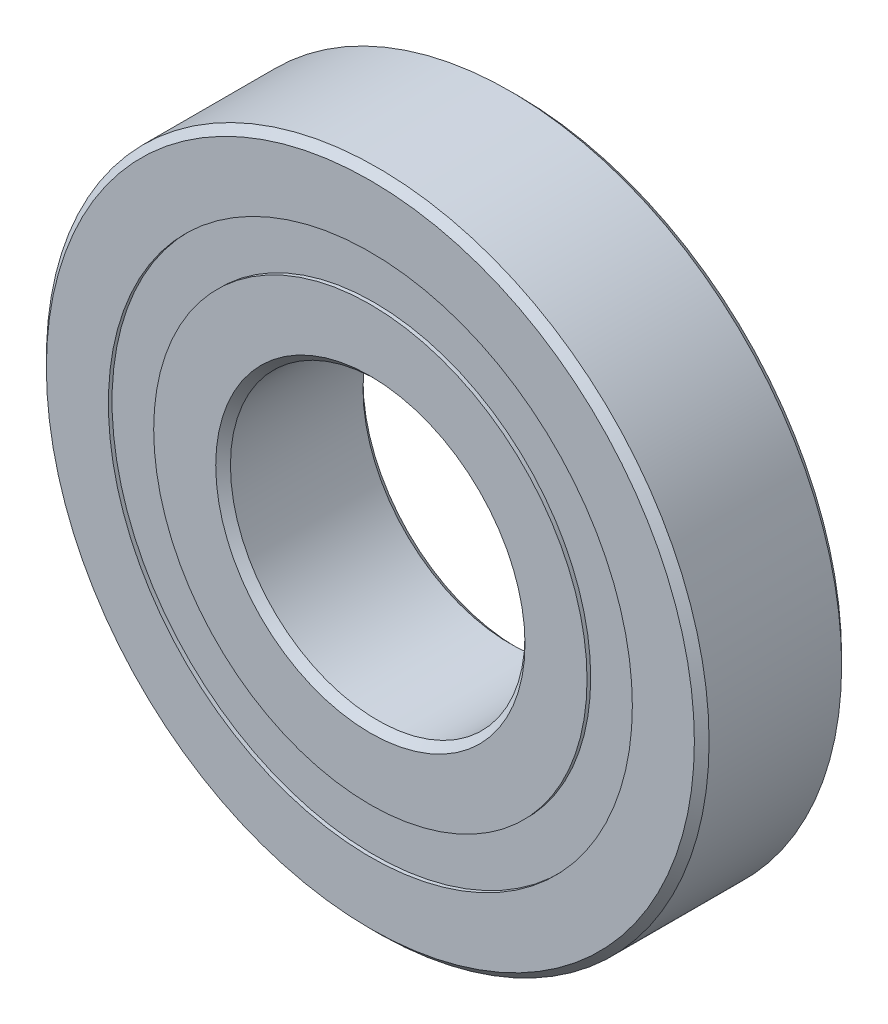
SolidWorks part; units mm, degrees
ref_plane "Front Plane" through (0, 0, 0) normal (0, 0, 1) x (1, 0, 0)
ref_plane "Top Plane" through (0, 0, 0) normal (0, 1, 0) x (1, 0, 0)
ref_plane "Right Plane" through (0, 0, 0) normal (1, 0, 0) x (0, 0, -1)
sketch "Sketch1" plane through (0, 0, 0) normal (1, 0, 0) x (0, 0, -1)
  line L0 (-3.175, 0) -> (3.175, 0) construction
  line L1 (0, 14.2875) -> (0, -14.2875) construction
  line L2 (2.8575, 14.2875) -> (-2.8575, 14.2875)
  line L3 (-2.8575, 14.2875) -> (-3.175, 13.97)
  line L4 (-3.175, 13.97) -> (-3.175, 11.2957)
  line L5 (-3.175, 11.2957) -> (-1.4111, 11.2957)
  line L6 (3.175, 11.2957) -> (1.4111, 11.2957)
  line L7 (3.175, 13.97) -> (3.175, 11.2957)
  line L8 (2.8575, 14.2875) -> (3.175, 13.97)
  line L9 (0, 14.2875) -> (0, 10.3187) construction
  line L10 (0, 10.3187) -> (0, 6.35) construction
  arc A0 (-1.4111, 11.2957) -> (1.4111, 11.2957) centre (0, 10.3187) cw
  point P14 (0, 6.35)
  dimension "Width" = 6.35
  dimension "OD" = 28.575
  dimension "D1" = 45
  dimension "D2" = 0.3175
  dimension "Shaft Dia" = 12.7
  dimension "D3" = 2.8222
  dimension "D4" = 0.9769
revolve "Revolve1" add sketch "Sketch1" angle 360 about L0
sketch "Sketch3" plane through (0, 0, 0) normal (1, 0, 0) x (0, 0, -1)
  line L0 (-3.175, 9.3418) -> (-1.4111, 9.3418)
  line L1 (0, 14.2875) -> (0, -14.2875) construction
  line L2 (-3.175, 13.97) -> (-3.175, 11.2957) construction
  line L3 (-3.175, 9.3418) -> (-3.175, 6.6675)
  line L4 (-2.8575, 14.2875) -> (-3.175, 13.97) construction
  line L5 (-3.175, 6.6675) -> (-2.8575, 6.35)
  line L6 (-2.8575, 6.35) -> (2.8575, 6.35)
  line L7 (2.8575, 14.2875) -> (2.8575, -14.2875) construction
  line L8 (2.8575, 6.35) -> (3.175, 6.6675)
  line L9 (3.175, -13.97) -> (3.175, 13.97) construction
  line L10 (3.175, 6.6675) -> (3.175, 9.3418)
  line L11 (3.175, 9.3418) -> (1.4111, 9.3418)
  line L13 (2.8575, 14.2875) -> (3.175, 13.97) construction
  arc A0 (1.4111, 11.2957) -> (-1.4111, 11.2957) centre (0, 10.3187) ccw construction
  arc A1 (1.4111, 9.3418) -> (-1.4111, 9.3418) centre (0, 10.3187) cw
revolve "Revolve3" add sketch "Sketch3" angle 360 about L0
sketch "Sketch4" plane through (0, 0, 0) normal (1, 0, 0) x (0, 0, -1)
  line L0 (-1.7163, 10.3187) -> (1.7163, 10.3187)
  arc A2 (-1.7163, 10.3187) -> (1.7163, 10.3187) centre (0, 10.3187) cw
  arc A3 (1.4111, 11.2957) -> (-1.4111, 11.2957) centre (0, 10.3187) ccw construction
revolve "Revolve4" add sketch "Sketch4" angle 360 about L0
ref_axis "Axis1" through (0, 0, -3.175) along (0, 0, 1)
pattern_circular "CirPattern1" count 10 every 36 about axis through (0, 0, -3.175) along (0, 0, 1) of bodies 104
sketch "Sketch5" plane through (0, 0, 0) normal (1, 0, 0) x (0, 0, -1)
  line L0 (-3.175, 11.2957) -> (-1.4111, 11.2957) construction
  line L1 (-3.0163, 11.2957) -> (-1.7163, 11.2957)
  line L2 (-3.0163, 11.2957) -> (-3.0163, 9.3418)
  line L3 (-3.0163, 9.3418) -> (-1.7163, 9.3418)
  line L4 (-1.7163, 11.2957) -> (-1.7163, 9.3418)
  line L5 (-3.175, 9.3418) -> (-1.4111, 9.3418) construction
  line L6 (3.175, 11.2957) -> (1.4111, 11.2957) construction
  line L7 (3.0163, 11.2957) -> (1.7163, 11.2957)
  line L8 (3.0163, 11.2957) -> (3.0163, 9.3418)
  line L9 (3.0163, 9.3418) -> (1.7163, 9.3418)
  line L10 (1.7163, 11.2957) -> (1.7163, 9.3418)
  line L11 (3.175, 9.3418) -> (1.4111, 9.3418) construction
  line L12 (-2.8575, 14.2875) -> (-3.175, 13.97) construction
  point P18 (-3.0163, 14.1287)
revolve "Revolve5" add sketch "Sketch5" angle 360 about L0
equation "\"D2@Sketch1\" = \"Width@Sketch1\"*.05"
equation "\"D3@Sketch1\" = \"Width@Sketch1\"/2.25"
equation "\"D4@Sketch1\" = (((\"OD@Sketch1\"-\"Width@Sketch1\")/2)/3.25)/3.5"
equation "\"D2@CirPattern1\" = 360/\"Balls@CirPattern1\""
